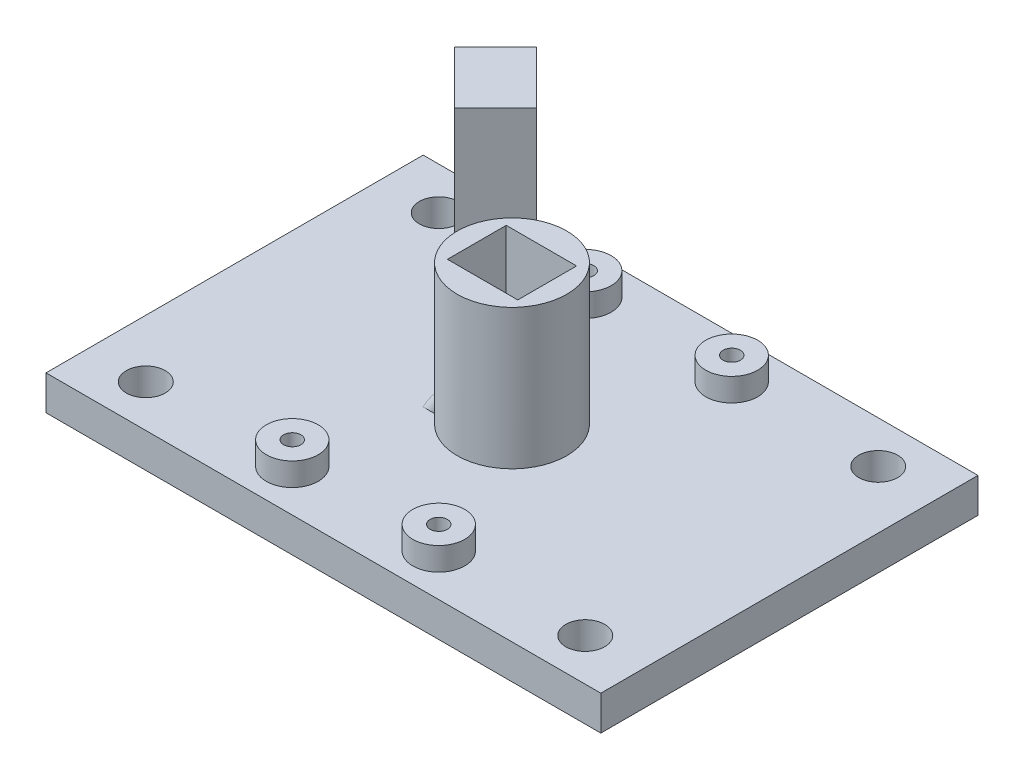
SolidWorks part; units mm, degrees
ref_plane "Front Plane" through (0, 0, 0) normal (0, 0, 1) x (1, 0, 0)
ref_plane "Top Plane" through (0, 0, 0) normal (0, 1, 0) x (1, 0, 0)
ref_plane "Right Plane" through (0, 0, 0) normal (1, 0, 0) x (0, 0, -1)
sketch "Sketch2" plane through (0, 0, 0) normal (0, 1, 0) x (1, 0, 0)
  line L6 (32.5319, 97.8554) -> (32.5319, 32.4554) construction
  line L7 (103.3319, 32.4554) -> (37.9319, 32.4554)
  line L8 (103.3319, 32.4554) -> (103.3319, 97.8554)
  line L9 (103.3319, 97.8554) -> (37.9319, 97.8554)
  line L10 (37.9319, 32.4554) -> (37.9319, 97.8554)
  line L13 (118.7319, 32.4554) -> (22.5319, 32.4554)
  line L14 (118.7319, 32.4554) -> (118.7319, 97.8554)
  line L15 (118.7319, 97.8554) -> (22.5319, 97.8554)
  line L16 (22.5319, 32.4554) -> (22.5319, 97.8554)
  line L19 (108.7319, 97.8554) -> (108.7319, 32.4554) construction
  line L20 (32.5319, 90.5554) -> (108.7319, 90.5554) construction
  line L21 (32.5319, 39.7554) -> (108.7319, 39.7554) construction
  circle A8 centre (32.5319, 90.5554) radius 3.3734
  circle A9 centre (32.5319, 39.7554) radius 3.3734
  circle A10 centre (108.7319, 90.5554) radius 3.3734
  circle A11 centre (108.7319, 39.7554) radius 3.3734
  circle A12 centre (70.6319, 65.1554) radius 1.5
  circle A13 centre (57.9319, 39.7554) radius 1.5
  circle A14 centre (83.3319, 39.7554) radius 1.5
  circle A15 centre (57.9319, 90.5554) radius 1.5
  circle A16 centre (83.3319, 90.5554) radius 1.5
  point P1 (108.7319, 65.1554)
  point P5 (70.6319, 65.1554)
  point P12 (70.6319, 39.7554)
  point P19 (70.6319, 65.1554)
  point P31 (32.5319, 65.1554)
  dimension "D3" = 6.7469
  dimension "D4" = 12.7
  dimension "D5" = 25.4
  dimension "D6" = 25.4
  dimension "D7" = 65.4
  dimension "D8" = 76.2
  dimension "D9" = 10
  dimension "D10" = 25.4
  dimension "D16" = 3
  dimension "D11" = 3
  dimension "D1" = 65.4
  dimension "D2" = 10
  dimension "D12" = 25.4
  dimension "D13" = 12.7
  dimension "D14" = 0
  dimension "D15" = 25.4
extrude "Boss-Extrude1" add sketch "Sketch2" along normal blind 6 contours L16 L13 L10 L15 A9 A8 | L13 L8 L15 A14 L10 | L15 L8 L9 L10 A14 | L13 L10 L7 L8 | L14 L15 L8 L13 A11 A10 | A12 region at (70.6319, 0, -33.3803) region at (111.2077, 0, -65.1554) region at (30.0561, 0, -65.1554) region at (70.6319, 0, -65.1554)
sketch "Sketch3" plane through (0, 6, 0) normal (0, 1, 0) x (1, 0, 0)
  circle A0 centre (83.3319, 39.7554) radius 1.5
  circle A1 centre (83.3319, 39.7554) radius 4.5
  circle A2 centre (83.3319, 39.7554) radius 1.5 construction
  dimension "D1" = 9
extrude "Boss-Extrude2" add sketch "Sketch3" along normal blind 4
ref_plane "Plane1" through (70.6319, 0, 0) normal (-1, 0, 0) x (0, 0, 1)
mirror "Mirror1" about plane through (70.6319, 0, 0) normal (-1, 0, 0) of "Boss-Extrude2"
ref_plane "Plane2" through (0, 0, -65.1554) normal (0, 0, -1) x (-1, 0, 0)
mirror "Mirror2" about plane through (0, 0, -65.1554) normal (0, 0, -1) of "Mirror1", "Boss-Extrude2"
sketch "Sketch6" plane through (0, 6, 0) normal (0, 1, 0) x (1, 0, 0)
  line L0 (22.5319, 97.8554) -> (118.7319, 32.4554) construction
  line L1 (22.5319, 32.4554) -> (118.7319, 97.8554) construction
  line L2 (74.3819, 70.2798) -> (66.8819, 70.2798)
  line L3 (66.8819, 60.0309) -> (74.3819, 60.0309)
  line L4 (66.8819, 70.2798) -> (62.6325, 70.2798)
  line L5 (66.8819, 60.0309) -> (62.6325, 60.0309)
  circle A0 centre (70.6319, 65.1554) radius 6.35
  circle A1 centre (70.6319, 65.1554) radius 9.5
  dimension "D1" = 12.7
  dimension "D2" = 19
  dimension "D3" = 7.5
  dimension "D4" = 7.5
extrude "Boss-Extrude3" add sketch "Sketch6" along normal blind 14 contours L2 A0 | L5 A1 L4 A0 | L3 A0 region at (70.6319, 6, -71.7637) region at (70.6319, 6, -70.7744) region at (70.6319, 6, -59.5364)
sketch "Sketch12" plane through (0, 6, 0) normal (0, 1, 0) x (1, 0, 0)
  line L0 (74.3819, 60.0309) -> (62.6325, 60.0309) construction
  line L1 (74.3819, 70.2798) -> (62.6325, 70.2798) construction
  line L2 (74.3819, 60.0309) -> (62.6325, 60.0309)
  line L3 (74.3819, 70.2798) -> (62.6325, 70.2798)
  arc A0 (74.3819, 60.0309) -> (74.3819, 70.2798) centre (70.6319, 65.1554) ccw construction
  arc A1 (74.3819, 60.0309) -> (74.3819, 70.2798) centre (70.6319, 65.1554) ccw
  circle A2 centre (70.6319, 65.1554) radius 6.35
  circle A3 centre (70.6319, 65.1554) radius 9.5
  line M13 (74.3819, 70.2798) -> (62.6325, 70.2798)
  line M15 (62.6325, 60.0309) -> (74.3819, 60.0309)
  arc M16 (74.3819, 60.0309) -> (74.3819, 70.2798) centre (70.6319, 65.1554) ccw
extrude "Cut-Extrude2" cut sketch "Sketch12" against normal blind 3 contours L3 A3 A2 M15 | A2 L2 M13 M16 region at (70.6319, 6, -65.1554) region at (63.3901, 6, -65.1554)
sketch "Sketch8" plane through (0, 3, 0) normal (0, 1, 0) x (1, 0, 0)
  line L1 (74.3819, 70.1554) -> (66.8819, 70.1554)
  line L2 (74.3819, 70.1554) -> (74.3819, 68.6554)
  line L3 (74.3819, 68.6554) -> (66.8819, 68.6554)
  line L4 (66.8819, 70.1554) -> (66.8819, 68.6554)
  line L5 (74.3819, 60.1554) -> (66.8819, 60.1554)
  line L6 (74.3819, 60.1554) -> (74.3819, 61.6554)
  line L7 (74.3819, 61.6554) -> (66.8819, 61.6554)
  line L8 (66.8819, 60.1554) -> (66.8819, 61.6554)
  dimension "D1" = 7.5
  dimension "D2" = 1.5
  dimension "D3" = 7.5
  dimension "D4" = 1.5
extrude "Boss-Extrude4" add sketch "Sketch8" along normal blind 3
sketch "Sketch9" plane through (0, 20, 0) normal (0, 1, 0) x (1, 0, 0)
  line L2 (62.6325, 70.2798) -> (74.3819, 70.2798)
  line L3 (74.3819, 60.0309) -> (62.6325, 60.0309)
  line L4 (62.6325, 70.2798) -> (74.3819, 70.2798)
  line L5 (74.3819, 60.0309) -> (62.6325, 60.0309)
  circle A0 centre (70.6319, 65.1554) radius 6.35
  circle A1 centre (70.6319, 65.1554) radius 9.5
  arc A2 (74.3819, 60.0309) -> (74.3819, 70.2798) centre (70.6319, 65.1554) ccw
  arc A3 (62.6325, 60.0309) -> (62.6325, 70.2798) centre (70.6319, 65.1554) ccw
  arc A4 (74.3819, 60.0309) -> (74.3819, 70.2798) centre (70.6319, 65.1554) ccw
  arc A5 (62.6325, 60.0309) -> (62.6325, 70.2798) centre (70.6319, 65.1554) ccw
  line M5 (62.6325, 70.2798) -> (74.3819, 70.2798)
  dimension "D1" = 0
extrude "Boss-Extrude5" add sketch "Sketch9" against normal blind 12 contours A1 L5 A0 M5 region at (63.3901, 20, -65.1554)
sketch "Sketch10" plane through (0, 20, 0) normal (0, 1, 0) x (1, 0, 0)
  line L1 (64.5319, 60.0554) -> (76.7319, 60.0554)
  line L2 (64.5319, 60.0554) -> (64.5319, 70.2554)
  line L3 (64.5319, 70.2554) -> (76.7319, 70.2554)
  line L4 (76.7319, 60.0554) -> (76.7319, 70.2554)
  line L5 (64.5319, 60.0554) -> (76.7319, 70.2554) construction
  line L6 (64.5319, 70.2554) -> (76.7319, 60.0554) construction
  circle A0 centre (70.6319, 65.1554) radius 9.5 construction
  circle A1 centre (70.6319, 65.1554) radius 9.5
  point P0 (70.6319, 65.1554)
  dimension "D1" = 10.2
  dimension "D2" = 12.2
extrude "Boss-Extrude6" add sketch "Sketch10" along normal blind 10.25
fillet "Fillet1" radius 2 1 edges at (61.1319, 6, -65.1554)
sketch "Sketch13" plane through (0, 6, 0) normal (0, 1, 0) x (1, 0, 0)
  line L5 (49.0931, 90.9089) -> (42.022, 83.8379)
  line L6 (42.022, 83.8379) -> (51.2144, 74.6455)
  line L7 (51.2144, 74.6455) -> (58.2854, 81.7166)
  line L8 (58.2854, 81.7166) -> (49.0931, 90.9089)
  line L9 (118.7319, 97.8554) -> (22.5319, 97.8554) construction
  line L10 (57.9319, 90.5554) -> (53.6892, 86.3128)
  circle A0 centre (57.9319, 90.5554) radius 1.5 construction
  circle A1 centre (57.9319, 90.5554) radius 1.5
  dimension "D4" = 6
  dimension "D1" = 45
  dimension "D2" = 13
  dimension "D3" = 10
extrude "Boss-Extrude7" add sketch "Sketch13" along normal blind 3 contours L7 L8 L5 L6 region at (50.1537, 6, -82.7772)
sketch "Sketch14" plane through (0, 9, 0) normal (0, 1, 0) x (1, 0, 0)
  line L0 (44.161, 81.6989) -> (49.8178, 87.3557)
  line L1 (49.8178, 87.3557) -> (54.7322, 82.4413)
  line L2 (54.7322, 82.4413) -> (49.0754, 76.7845)
  line L3 (42.022, 83.8379) -> (51.2144, 74.6455) construction
  line L15 (51.2144, 74.6455) -> (58.2854, 81.7166)
  line L16 (58.2854, 81.7166) -> (49.0931, 90.9089)
  line L17 (49.0931, 90.9089) -> (42.022, 83.8379)
  line L18 (42.022, 83.8379) -> (51.2144, 74.6455)
  line L19 (51.2144, 74.6455) -> (58.2854, 81.7166)
  line L20 (58.2854, 81.7166) -> (49.0931, 90.9089)
  line L21 (49.0931, 90.9089) -> (42.022, 83.8379)
  line L22 (42.022, 83.8379) -> (51.2144, 74.6455)
  point P5 (46.6182, 79.2417)
  dimension "D2" = 0
  dimension "D3" = 6.95
  dimension "D5" = 2
  dimension "D1" = 3.475
extrude "Boss-Extrude8" add sketch "Sketch14" along normal blind 2 contours L1 L2 L0 region at (43.2541, 9, -82.931)
sketch "Sketch15" plane through (0, 11, 0) normal (0, 1, 0) x (1, 0, 0)
  line L0 (49.8178, 87.3557) -> (51.2321, 88.7699)
  line L1 (54.7322, 82.4413) -> (56.1464, 83.8556)
  line L8 (49.8178, 87.3557) -> (54.7322, 82.4413)
  line L9 (54.7322, 82.4413) -> (49.0754, 76.7845)
  line L10 (49.0754, 76.7845) -> (51.2144, 74.6455)
  line L11 (51.2144, 74.6455) -> (58.2854, 81.7166)
  line L12 (58.2854, 81.7166) -> (49.0931, 90.9089)
  line L13 (49.0931, 90.9089) -> (42.022, 83.8379)
  line L14 (42.022, 83.8379) -> (44.161, 81.6989)
  line L15 (44.161, 81.6989) -> (49.8178, 87.3557)
  line L16 (49.8178, 87.3557) -> (54.7322, 82.4413)
  line L17 (54.7322, 82.4413) -> (49.0754, 76.7845)
  line L18 (49.0754, 76.7845) -> (51.2144, 74.6455)
  line L19 (51.2144, 74.6455) -> (58.2854, 81.7166)
  line L20 (58.2854, 81.7166) -> (49.0931, 90.9089)
  line L21 (49.0931, 90.9089) -> (42.022, 83.8379)
  line L22 (42.022, 83.8379) -> (44.161, 81.6989)
  line L23 (44.161, 81.6989) -> (49.8178, 87.3557)
  line M10 (54.7322, 82.4413) -> (49.0754, 76.7845)
  line M11 (49.0754, 76.7845) -> (51.2144, 74.6455)
  line M12 (51.2144, 74.6455) -> (58.2854, 81.7166)
  line M13 (58.2854, 81.7166) -> (49.0931, 90.9089)
  line M14 (49.0931, 90.9089) -> (42.022, 83.8379)
  line M15 (42.022, 83.8379) -> (44.161, 81.6989)
  line M16 (44.161, 81.6989) -> (49.8178, 87.3557)
  dimension "D1" = 0
extrude "Boss-Extrude9" add sketch "Sketch15" along normal blind 11 contours L0 M16 M13 M14 M15 | L1 M10 M11 M12 M13 region at (46.627, 11, -86.3039) region at (53.6804, 11, -79.2505)
sketch "Sketch16" plane through (0, 22, 0) normal (0, 1, 0) x (1, 0, 0)
  line L0 (42.022, 83.8379) -> (51.2144, 74.6455)
  line L1 (51.2144, 74.6455) -> (58.2854, 81.7166)
  line L2 (58.2854, 81.7166) -> (49.0931, 90.9089)
  line L3 (49.0931, 90.9089) -> (42.022, 83.8379)
extrude "Boss-Extrude10" add sketch "Sketch16" along normal blind 2
sketch "Sketch17" plane through (0, 24, 0) normal (0, 1, 0) x (1, 0, 0)
  line L0 (54.7322, 82.4413) -> (49.0754, 76.7845) construction
  line L1 (49.8178, 87.3557) -> (54.7322, 82.4413) construction
  line L2 (44.161, 81.6989) -> (49.8178, 87.3557) construction
  line L3 (54.7322, 82.4413) -> (49.0754, 76.7845)
  line L4 (49.0931, 90.9089) -> (42.022, 83.8379)
  line L5 (42.022, 83.8379) -> (51.2144, 74.6455)
  line L6 (51.2144, 74.6455) -> (58.2854, 81.7166)
  line L7 (58.2854, 81.7166) -> (49.0931, 90.9089)
  line L8 (49.0931, 90.9089) -> (42.022, 83.8379)
  line L9 (42.022, 83.8379) -> (51.2144, 74.6455)
  line L10 (51.2144, 74.6455) -> (58.2854, 81.7166)
  line L11 (58.2854, 81.7166) -> (49.0931, 90.9089)
  line L12 (49.8178, 87.3557) -> (54.7322, 82.4413)
  line L13 (44.161, 81.6989) -> (49.8178, 87.3557)
  line M5 (49.0931, 90.9089) -> (42.022, 83.8379)
  line M6 (42.022, 83.8379) -> (51.2144, 74.6455)
  line M7 (51.2144, 74.6455) -> (58.2854, 81.7166)
  line M8 (58.2854, 81.7166) -> (49.0931, 90.9089)
  dimension "D1" = 0
extrude "Boss-Extrude11" add sketch "Sketch17" along normal blind 2 contours L13 L12 L3 M6 M7 M8 M5 region at (52.4377, 24, -85.0612)
sketch "Sketch18" plane through (0, 26, 0) normal (0, 1, 0) x (1, 0, 0)
  line L0 (49.8178, 87.3557) -> (51.2321, 88.7699)
  line L1 (54.7322, 82.4413) -> (56.1464, 83.8556)
  line L8 (42.022, 83.8379) -> (44.161, 81.6989)
  line L9 (44.161, 81.6989) -> (49.8178, 87.3557)
  line L10 (49.8178, 87.3557) -> (54.7322, 82.4413)
  line L11 (54.7322, 82.4413) -> (49.0754, 76.7845)
  line L12 (49.0754, 76.7845) -> (51.2144, 74.6455)
  line L13 (51.2144, 74.6455) -> (58.2854, 81.7166)
  line L14 (58.2854, 81.7166) -> (49.0931, 90.9089)
  line L15 (49.0931, 90.9089) -> (42.022, 83.8379)
  line L16 (42.022, 83.8379) -> (44.161, 81.6989)
  line L17 (44.161, 81.6989) -> (49.8178, 87.3557)
  line L18 (49.8178, 87.3557) -> (54.7322, 82.4413)
  line L19 (54.7322, 82.4413) -> (49.0754, 76.7845)
  line L20 (49.0754, 76.7845) -> (51.2144, 74.6455)
  line L21 (51.2144, 74.6455) -> (58.2854, 81.7166)
  line L22 (58.2854, 81.7166) -> (49.0931, 90.9089)
  line L23 (49.0931, 90.9089) -> (42.022, 83.8379)
  line M9 (42.022, 83.8379) -> (44.161, 81.6989)
  line M10 (44.161, 81.6989) -> (49.8178, 87.3557)
  line M12 (54.7322, 82.4413) -> (49.0754, 76.7845)
  line M13 (49.0754, 76.7845) -> (51.2144, 74.6455)
  line M14 (51.2144, 74.6455) -> (58.2854, 81.7166)
  line M15 (58.2854, 81.7166) -> (49.0931, 90.9089)
  line M16 (49.0931, 90.9089) -> (42.022, 83.8379)
  dimension "D1" = 0
extrude "Boss-Extrude12" add sketch "Sketch18" along normal blind 11 contours L0 M10 M15 M16 M9 | L1 M12 M13 M14 M15 region at (46.627, 26, -86.3039) region at (53.6804, 26, -79.2505)
sketch "Sketch19" plane through (0, 37, 0) normal (0, 1, 0) x (1, 0, 0)
  line L0 (42.022, 83.8379) -> (51.2144, 74.6455)
  line L1 (51.2144, 74.6455) -> (58.2854, 81.7166)
  line L2 (58.2854, 81.7166) -> (49.0931, 90.9089)
  line L3 (49.0931, 90.9089) -> (42.022, 83.8379)
extrude "Boss-Extrude13" add sketch "Sketch19" along normal blind 2
sketch "Sketch11" plane through (0, 6, 0) normal (0, 1, 0) x (1, 0, 0)
  line L1 (80.4829, 74.6554) -> (60.7809, 74.6554)
  line L2 (80.4829, 74.6554) -> (80.4829, 55.6554)
  line L3 (80.4829, 55.6554) -> (60.7809, 55.6554)
  line L4 (60.7809, 74.6554) -> (60.7809, 55.6554)
  line L5 (80.4829, 74.6554) -> (60.7809, 55.6554) construction
  line L6 (80.4829, 55.6554) -> (60.7809, 74.6554) construction
  line L10 (22.5319, 97.8554) -> (22.5319, 32.4554)
  line L11 (22.5319, 32.4554) -> (118.7319, 32.4554)
  line L12 (118.7319, 32.4554) -> (118.7319, 97.8554)
  line L13 (118.7319, 97.8554) -> (22.5319, 97.8554)
  line L14 (22.5319, 97.8554) -> (22.5319, 32.4554)
  line L15 (22.5319, 32.4554) -> (118.7319, 32.4554)
  line L16 (118.7319, 32.4554) -> (118.7319, 97.8554)
  line L17 (118.7319, 97.8554) -> (22.5319, 97.8554)
  arc A0 (62.6325, 60.0309) -> (62.6325, 70.2798) centre (70.6319, 65.1554) ccw construction
  point P0 (70.6319, 65.1554)
  dimension "D1" = 0
extrude "Cut-Extrude1" [suppressed] cut sketch "Sketch11" against normal through all both and the other way through all
